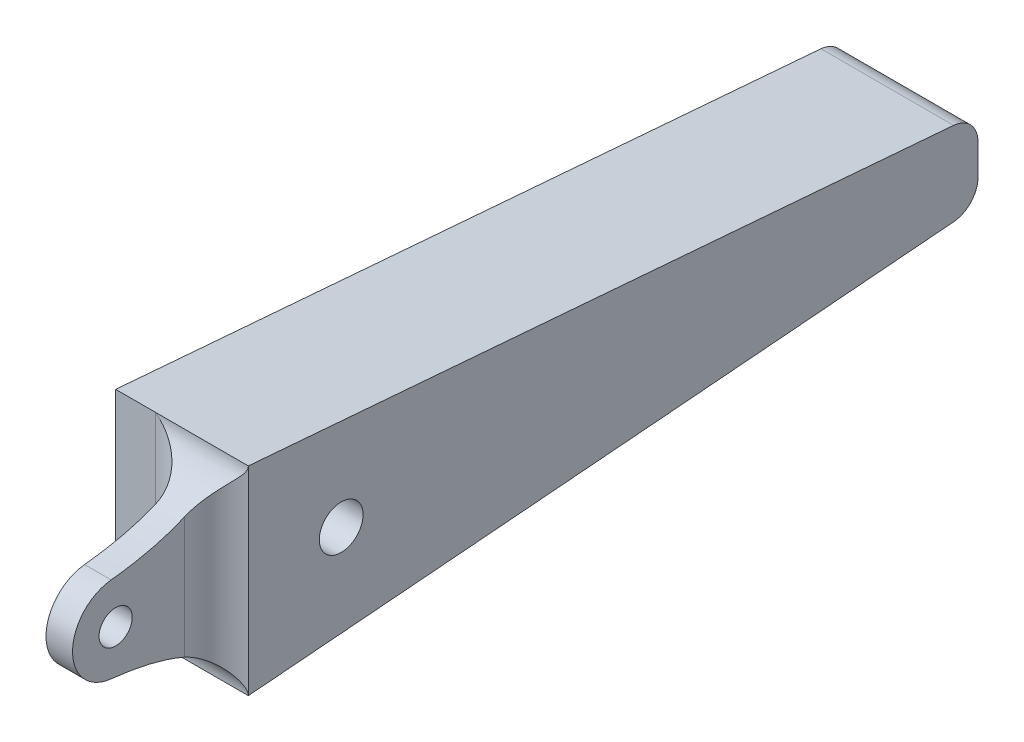
SolidWorks part; units mm, degrees
ref_plane "Front Plane" through (0, 0, 0) normal (1, 0, 0) x (0, 1, 0)
ref_plane "Top Plane" through (0, 0, 0) normal (0, 0, 1) x (0, 1, 0)
ref_plane "Right Plane" through (0, 0, 0) normal (0, 1, 0) x (-1, 0, 0)
sketch "Sketch1" plane through (0, 0, 0) normal (1, 0, 0) x (0, 1, 0)
  line L0 (0, -28.3905) -> (0, 48) construction
  line L1 (3, 0) -> (-3, 0)
  line L2 (-3, 0) -> (-7.5, 55)
  line L3 (3, 0) -> (7.5, 55)
  line L4 (0, 66.25) -> (0, 51.4514) construction
  circle A1 centre (0, 63) radius 1.25
  circle A2 centre (0, 48) radius 1.65
  arc A3 (3.2322, 63.3399) -> (-3.2322, 63.3399) centre (0, 63) ccw
  ellipse E0 centre (-7.5, 66.25) end of major axis (-7.5, 77.5) minor radius 4.4182 (-7.5, 55) -> (-3.2322, 63.3399) ccw
  ellipse E1 centre (7.5, 66.25) end of major axis (7.5, 77.5) minor radius 4.4182 (7.5, 55) -> (3.2322, 63.3399) cw
  point P9 (0, 0)
  dimension "D4" = 2.5
  dimension "D5" = 3.3
  dimension "D7" = 7
  dimension "D8" = 2
  dimension "D1" = 15
  dimension "D2" = 6
  dimension "D3" = 55
  dimension "D6" = 15
extrude "Boss-Extrude1" add sketch "Sketch1" along normal blind 10
fillet "Fillet3" radius 2 2 edges at (5, 3, 0) (5, -3, 0)
sketch "Sketch4" plane through (0, 0, 0) normal (0, 1, 0) x (-1, 0, 0)
  line L0 (-10, 66.25) -> (-10, 63.3399) construction
  line L1 (-10, 55) -> (0, 55) construction
  line L8 (-10, 66.25) -> (-8, 66.25)
  line L9 (-10, 66.25) -> (-10, 55)
  line L10 (-10, 55) -> (-8, 55)
  line L11 (-8, 66.25) -> (-8, 55)
  line L12 (0, 66.25) -> (-10, 66.25) construction
  line L14 (0, 66.25) -> (-6, 66.25)
  line L15 (0, 66.25) -> (0, 55)
  line L16 (0, 55) -> (-6, 55)
  line L17 (-6, 66.25) -> (-6, 55)
  dimension "D1" = 6
  dimension "D2" = 2
extrude "Cut-Extrude1" cut sketch "Sketch4" against normal through all and the other way through all contours L14 L17 L16 L15 | L11 L8 L9 L10
fillet "Fillet4" radius 3 2 edges at (6, 0, 55) (8, 0, 55)
